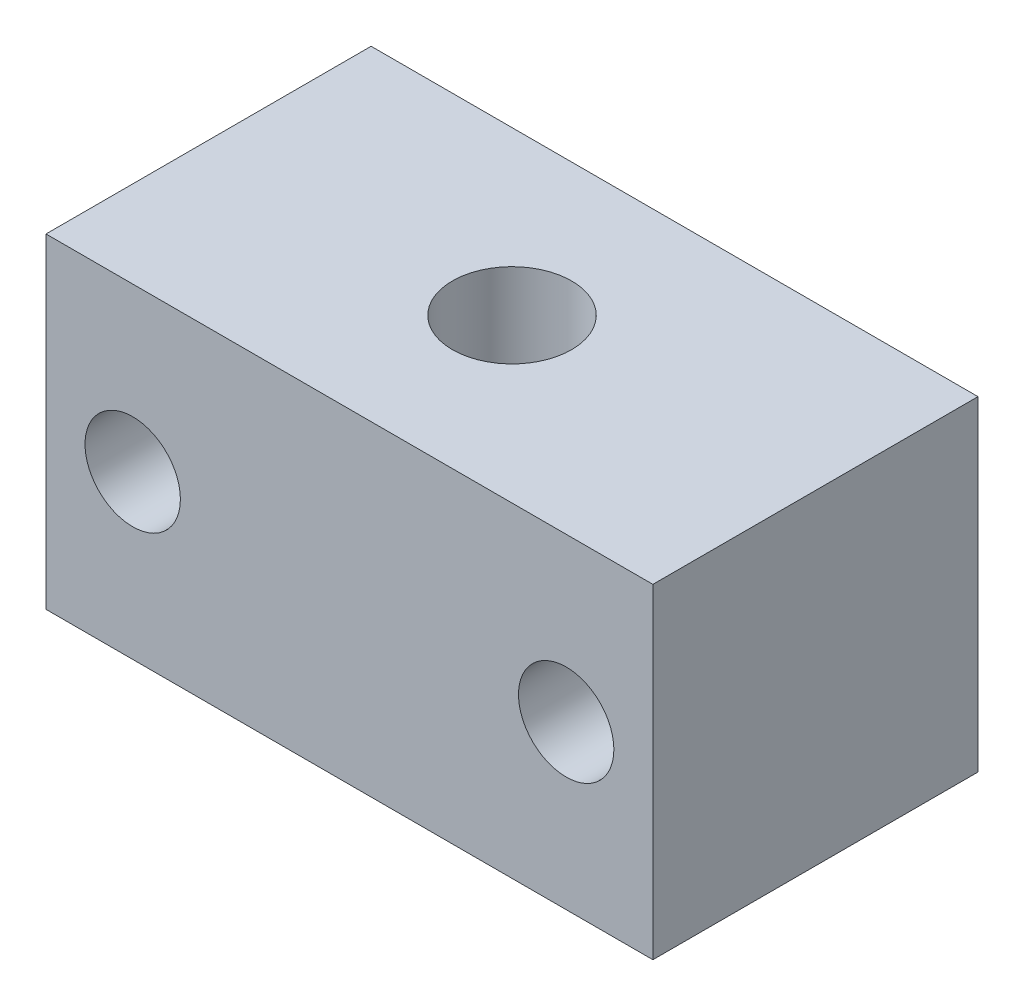
SolidWorks part; units mm, degrees
ref_plane "前视基准面" through (0, 0, 0) normal (0, 0, 1) x (1, 0, 0)
ref_plane "上视基准面" through (0, 0, 0) normal (0, 1, 0) x (1, 0, 0)
ref_plane "右视基准面" through (0, 0, 0) normal (1, 0, 0) x (0, 0, -1)
other "Configuration Table"
sketch "草图1" plane through (0, 0, 0) normal (0, 1, 0) x (1, 0, 0)
  line L1 (-14, -7.5) -> (14, -7.5)
  line L2 (-14, -7.5) -> (-14, 7.5)
  line L3 (-14, 7.5) -> (14, 7.5)
  line L4 (14, -7.5) -> (14, 7.5)
  line L5 (-14, -7.5) -> (14, 7.5) construction
  line L6 (-14, 7.5) -> (14, -7.5) construction
  circle A0 centre (0, 0) radius 2.75
  point P0 (0, 0)
  dimension "D3" = 5.5
  dimension "D1" = 28
  dimension "D2" = 15
extrude "凸台-拉伸1" add sketch "草图1" along normal mid plane 15
sketch "草图2" plane through (0, 0, 7.5) normal (0, 0, 1) x (1, 0, 0)
  circle A0 centre (-10, 0) radius 2.2
  circle A1 centre (10, 0) radius 2.2
  point P4 (0, 0)
  dimension "D1" = 4.4
  dimension "D2" = 20
  dimension "D3" = 10
extrude "切除-拉伸1" cut sketch "草图2" against normal blind 15
